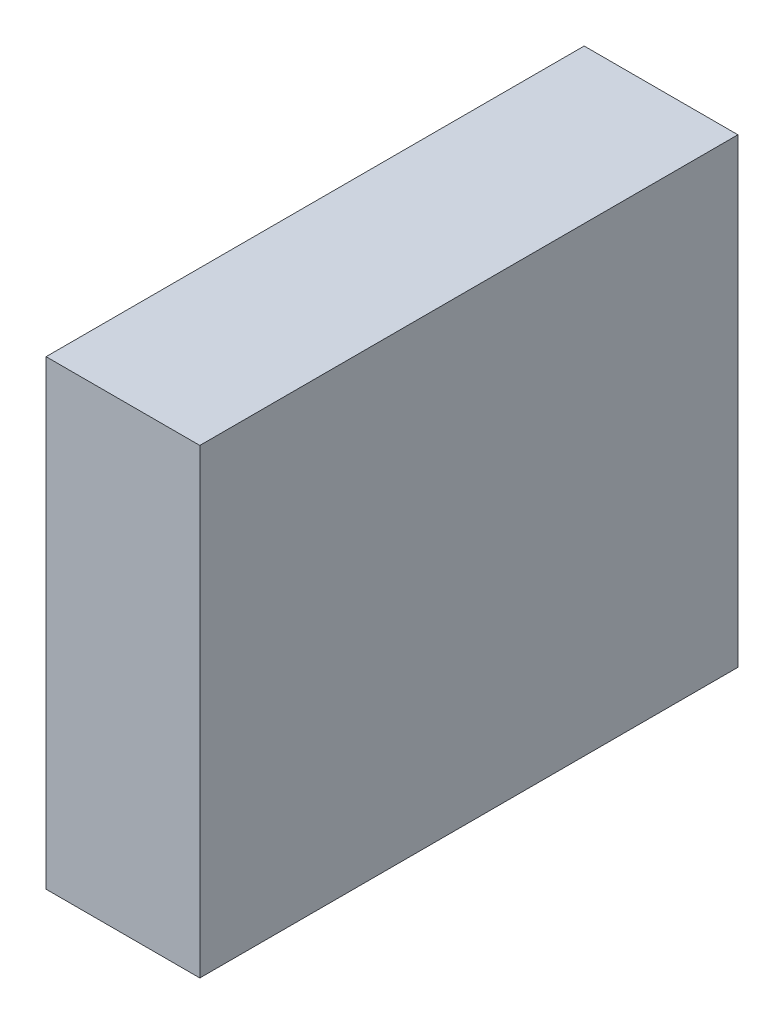
SolidWorks part; units mm, degrees
material "Maple"
ref_plane "Front Plane" through (0, 0, 0) normal (0, 0, 1) x (1, 0, 0)
ref_plane "Top Plane" through (0, 0, 0) normal (0, 1, 0) x (1, 0, 0)
ref_plane "Right Plane" through (0, 0, 0) normal (1, 0, 0) x (0, 0, -1)
sketch "Sketch1" plane through (0, 0, 0) normal (1, 0, 0) x (0, 0, -1)
  line L0 (0, 0) -> (44.45, 0)
  line L1 (0, 0) -> (0, 38.1)
  line L2 (44.45, 0) -> (44.45, 38.1)
  line L3 (0, 38.1) -> (44.45, 38.1)
  dimension "D1" = 44.45
  dimension "D2" = 38.1
extrude "Boss-Extrude1" add sketch "Sketch1" along normal blind 12.7
